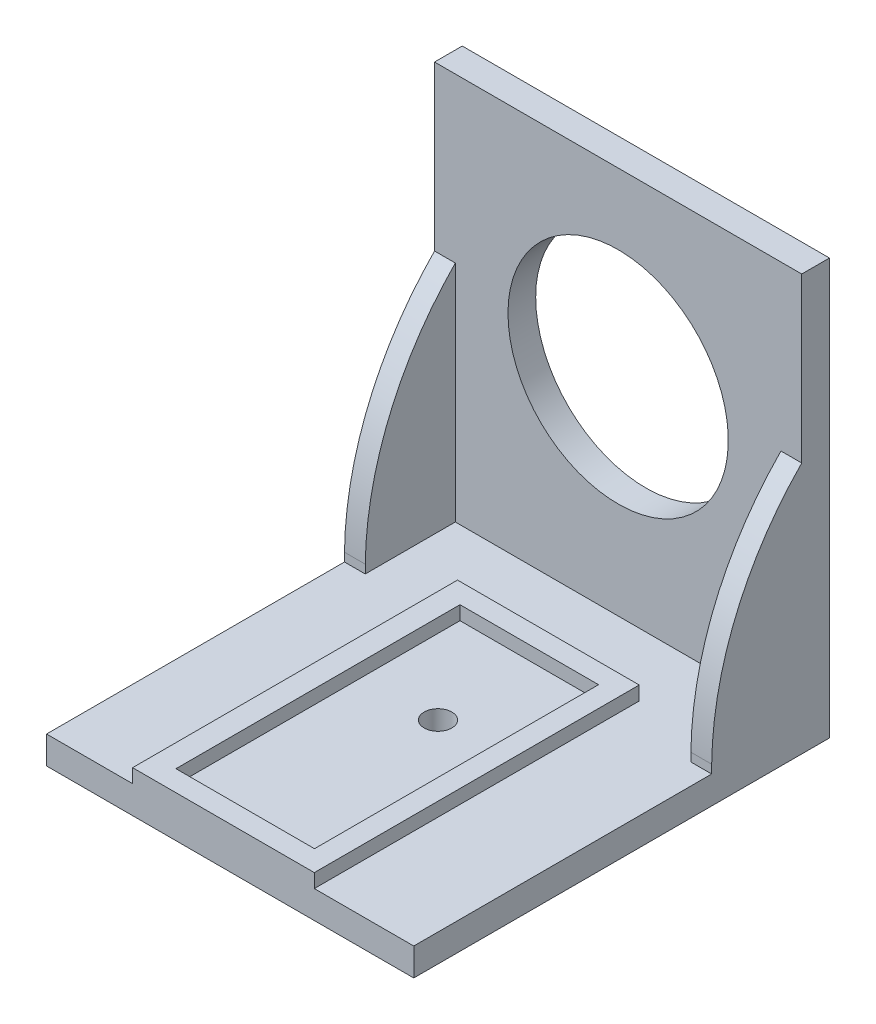
SolidWorks part; units mm, degrees
ref_plane "Plano frontal" through (0, 0, 0) normal (0, 0, 1) x (1, 0, 0)
ref_plane "Plano superior" through (0, 0, 0) normal (0, 1, 0) x (1, 0, 0)
ref_plane "Plano direito" through (0, 0, 0) normal (1, 0, 0) x (0, 0, -1)
sketch "Esboço1" plane through (0, 0, 0) normal (0, 0, 1) x (1, 0, 0)
  line L1 (0, 0) -> (53, 0)
  line L2 (0, 0) -> (0, 60)
  line L3 (0, 60) -> (53, 60)
  line L4 (53, 0) -> (53, 60)
  dimension "D1" = 53
  dimension "D2" = 60
extrude "Ressalto-extrusão1" add sketch "Esboço1" along normal blind 4
sketch "Esboço2" plane through (0, 0, 0) normal (0, 0, 1) x (1, 0, 0)
  line L0 (53, 0) -> (53, 60) construction
  line L1 (0, 0) -> (53, 0)
  line L2 (0, 0) -> (0, 4)
  line L3 (0, 4) -> (53, 4)
  line L4 (53, 0) -> (53, 4)
  dimension "D1" = 4
extrude "Ressalto-extrusão2" add sketch "Esboço2" along normal blind 60
sketch "Esboço5" plane through (0, 0, 0) normal (0, 0, 1) x (1, 0, 0)
  line L0 (0, 60) -> (0, 4) construction
  line L1 (0, 0) -> (53, 0) construction
  line L2 (0, 36.3739) -> (3, 36.3739)
  line L3 (0, 36.3739) -> (0, 0)
  line L4 (0, 0) -> (3, 0)
  line L5 (3, 36.3739) -> (3, 0)
  line L6 (0, 36.3739) -> (53, 36.3739) construction
  line L7 (53, 4) -> (53, 60) construction
  line L9 (53, 36.3739) -> (50, 36.3739)
  line L10 (53, 36.3739) -> (53, 0)
  line L11 (53, 0) -> (50, 0)
  line L12 (50, 36.3739) -> (50, 0)
  dimension "D1" = 3
  dimension "D2" = 3
extrude "Ressalto-extrusão3" add sketch "Esboço5" along normal blind 17
sketch "Esboço6" plane through (0, 0, 0) normal (1, 0, 0) x (0, 0, -1)
  line L0 (-4, 36.3739) -> (-17, 36.3739)
  line L1 (-17, 36.3739) -> (-17, 4)
  arc A0 (-17, 4) -> (-4, 36.3739) centre (28.283, 4.6133) cw
extrude "Corte-extrusão3" cut sketch "Esboço6" along direction (1, 0, 0) on the side of the normal blind 62 and the other way blind 15 contours L1 A0 L0 region at (0, 28.6879, 13.2183)
sketch "Esboço7" plane through (0, 0, 0) normal (0, 1, 0) x (1, 0, 0)
  line L0 (26.5, 0) -> (26.5, -60) construction
  line L1 (53, 0) -> (0, 0) construction
  line L2 (53, -60) -> (0, -60) construction
  line L4 (15.6741, -57) -> (35.6741, -57)
  line L5 (15.6741, -57) -> (15.6741, -16)
  line L6 (15.6741, -16) -> (35.6741, -16)
  line L7 (35.6741, -57) -> (35.6741, -16)
  line L8 (12.4175, -60) -> (38.6461, -60)
  line L9 (12.4175, -60) -> (12.4175, -13.1011)
  line L10 (12.4175, -13.1011) -> (38.6461, -13.1011)
  line L11 (38.6461, -60) -> (38.6461, -13.1011)
  circle A0 centre (26.5, -30) radius 2
  dimension "D1" = 4
  dimension "D2" = 20
  dimension "D3" = 41
  dimension "D4" = 12
extrude "Ressalto-extrusão4" add sketch "Esboço7" along direction (0, -1, 0) on the side of the normal blind 6 contours L9 L10 L11 L8 | L5 L6 L7 L4
sketch "Esboço8" plane through (0, 0, 0) normal (0, 1, 0) x (1, 0, 0)
  line L0 (26.5, 0) -> (26.5, -60) construction
  line L1 (53, 0) -> (0, 0) construction
  line L2 (12.4175, -60) -> (38.6461, -60) construction
  circle A0 centre (26.5, -30) radius 2
  dimension "D1" = 4
extrude "Corte-extrusão4" cut sketch "Esboço8" along direction (0, -1, 0) on the side of the normal blind 10 and the other way blind 21
sketch "Esboço9" plane through (0, 0, 0) normal (0, 0, 1) x (1, 0, 0)
  line L0 (26.5, 0) -> (26.5, 60) construction
  line L1 (0, 0) -> (53, 0) construction
  line L2 (53, 60) -> (0, 60) construction
  circle A0 centre (26.5, 33.9) radius 15.9
  dimension "D2" = 31.8
  dimension "D1" = 33.9
extrude "Corte-extrusão6" cut sketch "Esboço9" along direction (0, 0, -1) on the side of the normal blind 45 and the other way blind 37
